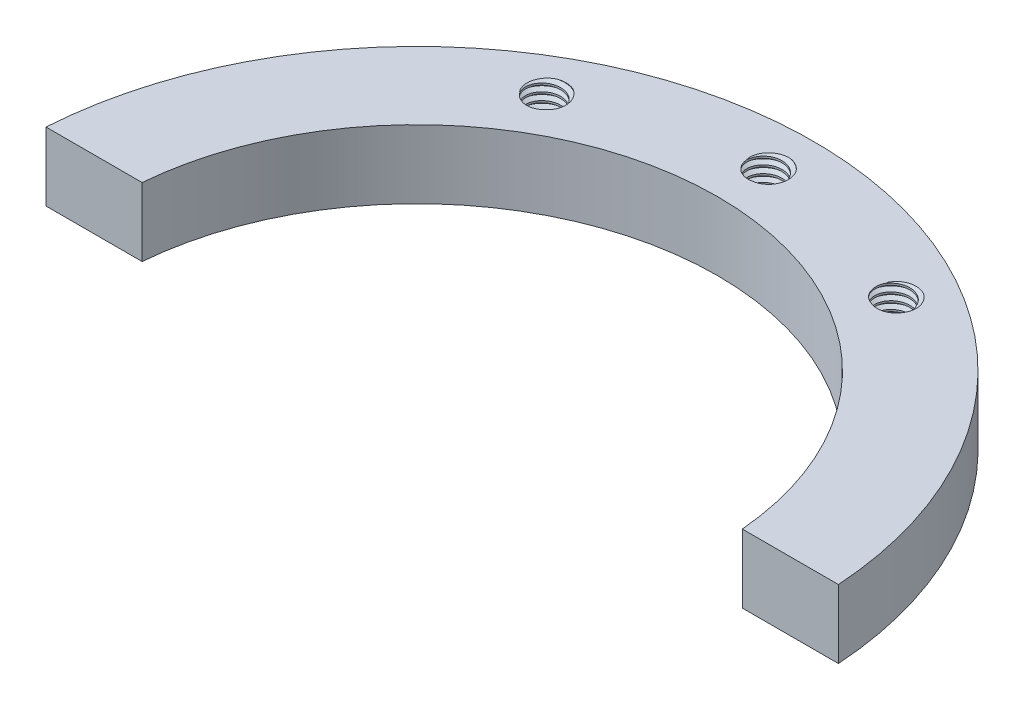
SolidWorks part; units mm, degrees
ref_plane "Front Plane" through (0, 0, 0) normal (0, 0, 1) x (1, 0, 0)
ref_plane "Top Plane" through (0, 0, 0) normal (0, 1, 0) x (1, 0, 0)
ref_plane "Right Plane" through (0, 0, 0) normal (1, 0, 0) x (0, 0, -1)
sketch "Sketch1" plane through (0, 0, 0) normal (0, 1, 0) x (1, 0, 0)
  circle A0 centre (0, 0) radius 57.15 construction
  circle A1 centre (0, 0) radius 73.66
  circle A2 centre (0, 0) radius 55.88
  dimension "D1" = 114.3
  dimension "D2" = 1.27
  dimension "D3" = 17.78
extrude "Boss-Extrude1" add sketch "Sketch1" along normal blind 12.7
sketch "Sketch3" plane through (0, 12.7, 0) normal (0, 1, 0) x (1, 0, 0)
  line L0 (-55, 0) -> (55, 0) construction
  line L1 (-87.1123, 4.7625) -> (87.0672, 4.7625)
  line L2 (-87.1123, 4.7625) -> (-87.1123, -90.3663)
  line L3 (-87.1123, -90.3663) -> (87.0672, -90.3663)
  line L4 (87.0672, 4.7625) -> (87.0672, -90.3663)
  dimension "D1" = 4.7625
extrude "Cut-Extrude1" cut sketch "Sketch3" against normal up to next
ref_plane "Plane1" through (0, 0, -73.66) normal (0, 0, -1) x (-1, 0, 0)
hole_wizard "5/16-18 Tapped Hole1" positions "3DSketch1" profile "Sketch6" tap size "5/16-18" standard "ANSI Inch" end condition up to next
sketch3d "3DSketch1"
  line L2 (0, 12.7, -73.66) -> (0, 12.7, -55.88) construction
  arc A0 (73.5059, 12.7, -4.7625) -> (-73.5059, 12.7, -4.7625) centre (0, 12.7, 0) ccw construction
  arc A1 (55.6767, 12.7, -4.7625) -> (-55.6767, 12.7, -4.7625) centre (0, 12.7, 0) ccw construction
  point P0 (0, 12.7, -64.77)
  point P12 (0, 86.36, 0)
  point P16 (0, 68.58, 0)
  point P18 (0, 0, 0)
  point P19 (0, 0, 0)
  point P20 (0, 0, 0)
sketch "Sketch6" plane through (0, 12.7, -64.77) normal (1, 0, 0) x (0, 0, 1)
  line L0 (0, 0) -> (0, 12.7)
  line L1 (0, 12.7) -> (3.2639, 12.7)
  line L2 (3.2639, 12.7) -> (3.2639, 0)
  line L5 (3.2639, 0) -> (0, 0)
  line L11 (0, -6.35) -> (0, 107.95) construction
  dimension "Thru Tap Drill Dia." = 6.5278
  dimension "Thru Tap Drill Depth" = 12.7
thread "Thread1" pitch 1.4111 method cut profile "Thread Profile1" start angle 0, offset 1, length 20, pitch 1.4111, diameter 6.5278
ref_plane "Plane2" through (-3.2639, 13.7, -64.77) normal (0, 0, 1) x (-1, 0, 0)
sketch "Thread Profile1" plane through (-3.2639, 13.7, -64.77) normal (0, 0, 1) x (-1, 0, 0)
  line L0 (0, 0) -> (0, 1.4111) construction
  line L1 (0, 0) -> (0.7638, 0.441)
  line L2 (0.7638, 0.441) -> (0.7638, 0.6174)
  line L3 (0.7638, 0.6174) -> (0, 1.0583)
  line L4 (0.7638, 0.5292) -> (0, 0.5292) construction
  line L11 (0, 0) -> (0, 1.0583)
  point P2 (0, 0)
  dimension "Pitch" = 1.4111
  dimension "Profile_Angle" = 60
  dimension "Profile_Land" = 0.1764
  dimension "Profile_Height" = 0.7638
pattern_circular "CirPattern1" count 2 every 30 about axis through (0, 12.7, 0) along (0, -1, 0) of "5/16-18 Tapped Hole1", "Thread1" other way count 2
